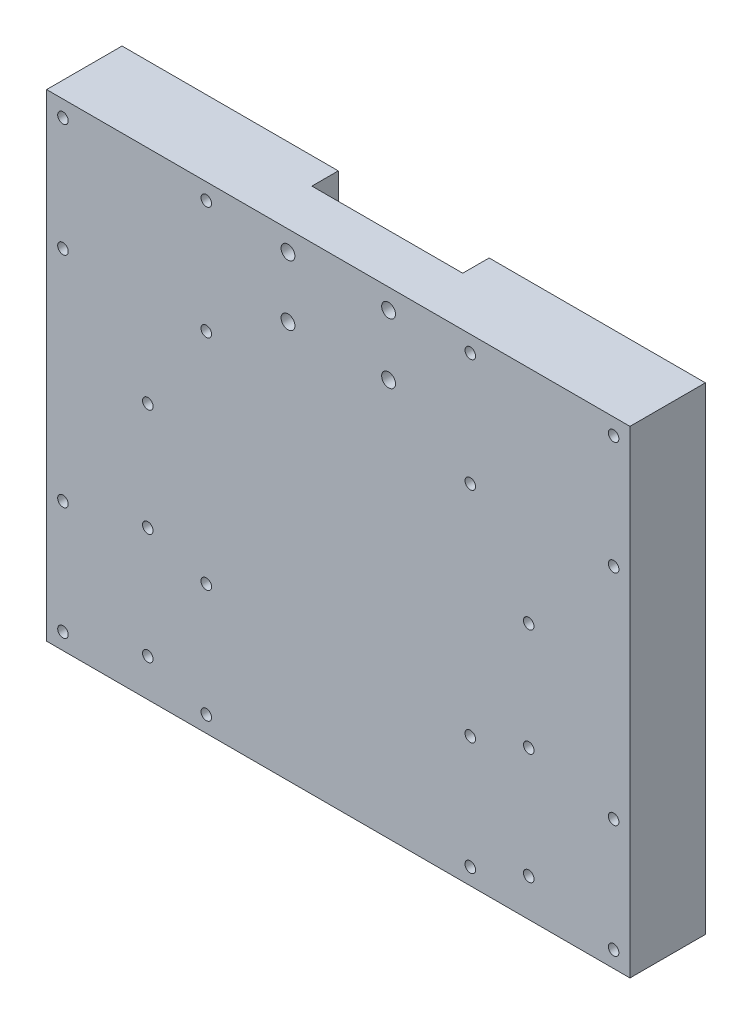
SolidWorks part; units mm, degrees
ref_plane "Piano frontale" through (0, 0, 0) normal (0, 0, 1) x (1, 0, 0)
ref_plane "Piano superiore" through (0, 0, 0) normal (0, 1, 0) x (1, 0, 0)
ref_plane "Piano destro" through (0, 0, 0) normal (1, 0, 0) x (0, 0, -1)
sketch "Schizzo1" plane through (0, 0, 0) normal (0, 0, 1) x (1, 0, 0)
  line L1 (116, -95) -> (-116, -95)
  line L2 (116, -95) -> (116, 95)
  line L3 (116, 95) -> (-116, 95)
  line L4 (-116, -95) -> (-116, 95)
  line L5 (116, -95) -> (-116, 95) construction
  line L6 (116, 95) -> (-116, -95) construction
  point P0 (0, 0)
  dimension "D1" = 232
  dimension "D2" = 190
extrude "Estrusione-Estrusione1" add sketch "Schizzo1" along normal blind 30
sketch "Schizzo3" plane through (0, 0, 30) normal (0, 0, 1) x (1, 0, 0)
  line L0 (20, 7) -> (-20, 7) construction
  line L1 (-20, 7) -> (20, -17) construction
  line L2 (20, -17) -> (20, 7) construction
  line L3 (20, 7) -> (-20, -17) construction
  line L4 (-20, -17) -> (-20, 7) construction
  line L5 (-20, -17) -> (20, -17) construction
  circle A8 centre (20, 7) radius 3
  circle A9 centre (-20, 7) radius 3
  circle A10 centre (-20, -17) radius 3
  circle A11 centre (20, -17) radius 3
  point P21 (0, -5)
  dimension "D1" = 40
  dimension "D2" = 24
sketch "Schizzo4" plane through (0, 95, 0) normal (0, 1, 0) x (1, 0, 0)
  line L0 (116, 0) -> (-116, 0) construction
  line L1 (30, 0) -> (-30, 0)
  line L2 (30, 0) -> (30, -10.5)
  line L3 (30, -10.5) -> (-30, -10.5)
  line L4 (-30, 0) -> (-30, -10.5)
  dimension "D1" = 10.5
extrude "Taglio-Estrusione2" cut sketch "Schizzo4" against normal through all
sketch "Sketch1" plane through (0, 0, 0) normal (0, 0, -1) x (-1, 0, 0)
  point P0 (-109.5, 88.5)
  point P1 (-109.5, 43.5)
  point P3 (-52.5, 88.5)
  point P5 (-52.5, 43.5)
  point P7 (-52.5, -43.5)
  point P9 (-109.5, -43.5)
  point P11 (-109.5, -88.5)
  point P13 (-52.5, -88.5)
  point P15 (52.5, -88.5)
  point P17 (109.5, -88.5)
  point P19 (109.5, -43.5)
  point P21 (52.5, -43.5)
  point P23 (52.5, 43.5)
  point P25 (109.5, 43.5)
  point P27 (109.5, 88.5)
  point P29 (52.5, 88.5)
hole_wizard "Tap Drill for M5 Tap1" positions "Sketch2" profile "Sketch3" hole size "M5" standard "ISO" end condition through all
sketch "Sketch2" plane through (0, 0, 0) normal (0, 0, -1) x (-1, 0, 0)
  point P0 (-109.5, 88.5)
  point P3 (-109.5, 43.5)
  point P6 (-52.5, 43.5)
  point P9 (-52.5, 88.5)
  point P12 (52.5, 88.5)
  point P15 (109.5, 88.5)
  point P18 (109.5, 43.5)
  point P21 (52.5, 43.5)
  point P24 (52.5, -43.5)
  point P27 (109.5, -43.5)
  point P30 (109.5, -88.5)
  point P33 (52.5, -88.5)
  point P36 (-52.5, -88.5)
  point P39 (-52.5, -43.5)
  point P42 (-109.5, -43.5)
  point P45 (-109.5, -88.5)
sketch "Sketch3" plane through (109.5, 88.5, 0) normal (1, 0, 0) x (0, 1, 0)
  line L0 (0, 0) -> (0, 30)
  line L1 (0, 30) -> (2.1, 30)
  line L2 (2.1, 30) -> (2.1, 0)
  line L5 (2.1, 0) -> (0, 0)
  line L11 (0, -6.35) -> (0, 107.95) construction
  dimension "Thru Hole Dia." = 4.2
  dimension "Thru Hole Depth" = 30
hole_wizard "M5 Clearance Hole1" positions "Sketch4" profile "Sketch5" hole size "M5" standard "ISO" end condition through all
sketch "Sketch4" plane through (0, 0, 30) normal (0, 0, 1) x (1, 0, 0)
  point P0 (-20, 87)
  point P3 (20, 87)
  point P6 (20, 63)
  point P9 (-20, 63)
  point P10 (0, 0)
  point P11 (0, 0)
  point P12 (0, 0)
  point P13 (0, 0)
  point P14 (0, 0)
sketch "Sketch5" plane through (-20, 87, 30) normal (1, 0, 0) x (0, -1, 0)
  line L0 (0, 0) -> (0, 30)
  line L1 (0, 30) -> (2.75, 30)
  line L2 (2.75, 30) -> (2.75, 0)
  line L5 (2.75, 0) -> (0, 0)
  line L11 (0, -6.35) -> (0, 107.95) construction
  dimension "Thru Hole Dia." = 5.5
  dimension "Thru Hole Depth" = 30
hole_wizard "Tap Drill for M5 Tap3" positions "Sketch6" profile "Sketch7" hole size "M5" standard "ISO" end condition up to next
sketch "Sketch6" plane through (0, 0, 30) normal (0, 0, 1) x (1, 0, 0)
  point P0 (-75.75, 7)
  point P6 (-75.75, -80)
  point P8 (75.75, 7)
  point P14 (75.75, -80)
  point P23 (-75.75, -35.7925)
  point P25 (75.75, -35.7925)
sketch "Sketch7" plane through (-75.75, 7, 30) normal (1, 0, 0) x (0, -1, 0)
  line L0 (0, 0) -> (0, 30)
  line L1 (0, 30) -> (2.1, 30)
  line L2 (2.1, 30) -> (2.1, 0)
  line L5 (2.1, 0) -> (0, 0)
  line L11 (0, -6.35) -> (0, 107.95) construction
  dimension "Thru Hole Dia." = 4.2
  dimension "Thru Hole Depth" = 30
